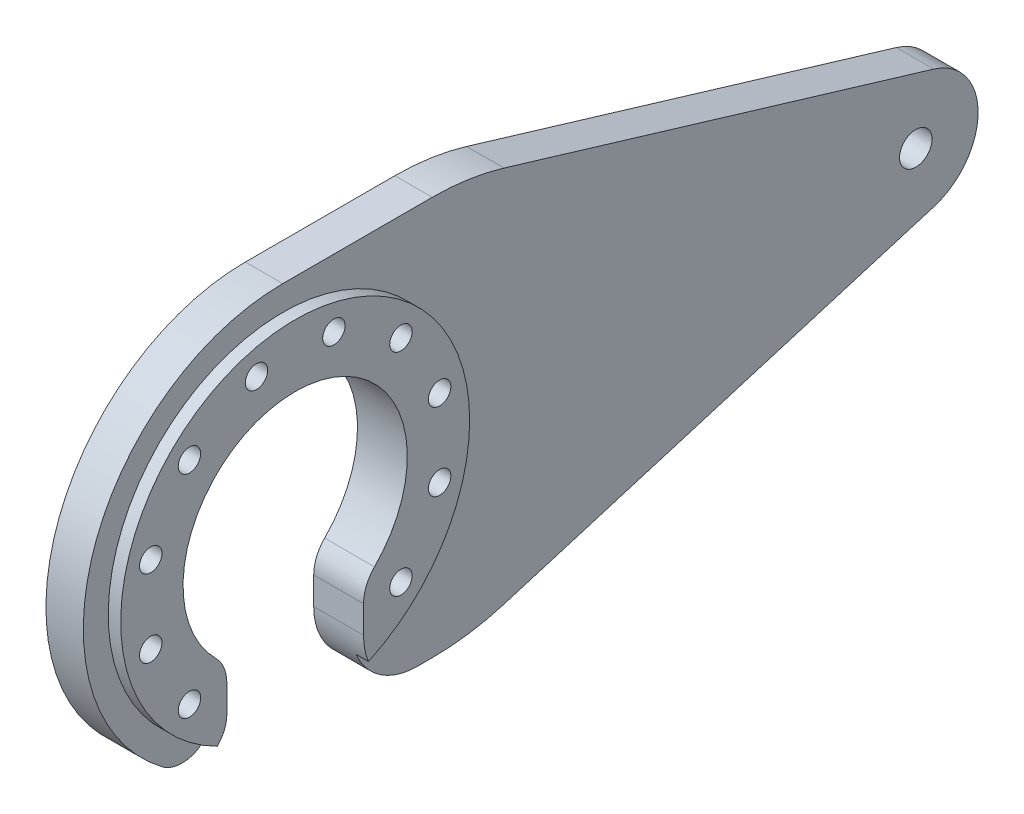
SolidWorks part; units mm, degrees
ref_plane "Front Plane" through (0, 0, 0) normal (0, 0, 1) x (1, 0, 0)
ref_plane "Top Plane" through (0, 0, 0) normal (0, 1, 0) x (1, 0, 0)
ref_plane "Right Plane" through (0, 0, 0) normal (1, 0, 0) x (0, 0, -1)
sketch "Sketch1" plane through (0, 0, 0) normal (-1, 0, 0) x (0, 0, 1)
  circle A0 centre (0, 0) radius 22.5
  circle A1 centre (0, 0) radius 35
  circle A2 centre (21.2132, -21.2132) radius 2.25 construction
  circle A3 centre (28.9778, -7.7646) radius 2.25 construction
  circle A4 centre (28.9778, 7.7646) radius 2.25 construction
  circle A5 centre (21.2132, 21.2132) radius 2.25 construction
  circle A6 centre (7.7646, 28.9778) radius 2.25 construction
  circle A7 centre (-7.7646, 28.9778) radius 2.25 construction
  circle A8 centre (-21.2132, 21.2132) radius 2.25 construction
  circle A9 centre (-28.9778, 7.7646) radius 2.25 construction
  circle A10 centre (-28.9778, -7.7646) radius 2.25 construction
  circle A11 centre (-21.2132, -21.2132) radius 2.25 construction
  circle A12 centre (-21.2132, -21.2132) radius 2.25
  circle A13 centre (-28.9778, -7.7646) radius 2.25
  circle A14 centre (-28.9778, 7.7646) radius 2.25
  circle A15 centre (-21.2132, 21.2132) radius 2.25
  circle A16 centre (-7.7646, 28.9778) radius 2.25
  circle A17 centre (7.7646, 28.9778) radius 2.25
  circle A18 centre (21.2132, 21.2132) radius 2.25
  circle A19 centre (28.9778, 7.7646) radius 2.25
  circle A20 centre (28.9778, -7.7646) radius 2.25
  circle A21 centre (21.2132, -21.2132) radius 2.25
  dimension "D1" = 45
  dimension "D2" = 70
extrude "Boss-Extrude1" add sketch "Sketch1" along normal blind 2.5
sketch "Sketch2" plane through (-2.5, 0, 0) normal (-1, 0, 0) x (0, 0, 1)
  line L0 (0, 40) -> (-30, 40)
  line L1 (-44.3935, 37.8835) -> (-130.5984, 11.9709)
  line L2 (-130.5984, -11.9709) -> (-44.3935, -37.8835)
  line L3 (-30, -40) -> (0, -40)
  arc A0 (-30, 40) -> (-44.3935, 37.8835) centre (-30, -10) ccw
  circle A1 centre (0, 0) radius 22.5
  circle A2 centre (0, 0) radius 22.5
  circle A3 centre (-21.2132, -21.2132) radius 2.25
  circle A4 centre (-21.2132, -21.2132) radius 2.25
  circle A5 centre (-28.9778, -7.7646) radius 2.25
  circle A6 centre (-28.9778, -7.7646) radius 2.25
  circle A7 centre (-28.9778, 7.7646) radius 2.25
  circle A8 centre (-28.9778, 7.7646) radius 2.25
  circle A9 centre (-21.2132, 21.2132) radius 2.25
  circle A10 centre (-21.2132, 21.2132) radius 2.25
  circle A11 centre (-7.7646, 28.9778) radius 2.25
  circle A12 centre (-7.7646, 28.9778) radius 2.25
  circle A13 centre (7.7646, 28.9778) radius 2.25
  circle A14 centre (7.7646, 28.9778) radius 2.25
  circle A15 centre (21.2132, 21.2132) radius 2.25
  circle A16 centre (21.2132, 21.2132) radius 2.25
  circle A17 centre (28.9778, 7.7646) radius 2.25
  circle A18 centre (28.9778, 7.7646) radius 2.25
  circle A19 centre (28.9778, -7.7646) radius 2.25
  circle A20 centre (28.9778, -7.7646) radius 2.25
  circle A21 centre (21.2132, -21.2132) radius 2.25
  circle A22 centre (21.2132, -21.2132) radius 2.25
  arc A23 (-130.5984, 11.9709) -> (-130.5984, -11.9709) centre (-127, 0) ccw
  arc A24 (-44.3935, -37.8835) -> (-30, -40) centre (-30, 10) ccw
  arc A25 (0, -40) -> (0, 40) centre (0, 0) ccw
  circle A26 centre (-127, 0) radius 3.2639
  dimension "D12" = 40
  dimension "D13" = 12.5
  dimension "D14" = 50
  dimension "D17" = 6.5278
  dimension "D15" = 30
  dimension "D16" = 127
  dimension "D1" = 0
  dimension "D2" = 0
  dimension "D3" = 0
  dimension "D4" = 0
  dimension "D5" = 0
  dimension "D6" = 0
  dimension "D7" = 0
  dimension "D8" = 0
  dimension "D9" = 0
  dimension "D10" = 0
  dimension "D11" = 0
extrude "Boss-Extrude2" add sketch "Sketch2" along normal offset from surface (7.5 mm away) 10 up to face at (0, 0, 35)
sketch "Sketch3" plane through (0, 0, 0) normal (1, 0, 0) x (0, 0, -1)
  line L0 (30, -40) -> (0, -40) construction
  line L1 (26.9985, -40) -> (0, -40)
  line L3 (13.7132, -21.2132) -> (13.7132, -26.7147)
  line L4 (-13.7132, -21.2132) -> (-13.7132, -26.7147)
  circle A0 centre (0, 0) radius 22.5 construction
  arc A1 (-15.9099, -15.9099) -> (15.9099, -15.9099) centre (0, 0) ccw
  arc A2 (-15.9099, -15.9099) -> (-13.7132, -21.2132) centre (-21.2132, -21.2132) cw
  arc A4 (13.7132, -21.2132) -> (15.9099, -15.9099) centre (21.2132, -21.2132) cw
  circle A5 centre (-21.2132, -21.2132) radius 2.25 construction
  arc A9 (13.7132, -26.7147) -> (26.9985, -40) centre (26.9985, -26.7147) ccw
  arc A10 (0, 40) -> (0, -40) centre (0, 0) ccw construction
  arc A11 (-24.1352, -31.8982) -> (0, -40) centre (0, 0) ccw
  arc A12 (-13.7132, -26.7147) -> (-24.1352, -31.8982) centre (-20.2132, -26.7147) cw
  point P15 (-23.6942, -32.2271)
  point P18 (0, 0)
  point P19 (13.7132, -26.868)
  dimension "D1" = 6.5
extrude "Cut-Extrude1" cut sketch "Sketch3" against normal through all
sketch "Sketch4" plane through (-10, 0, 0) normal (-1, 0, 0) x (0, 0, 1)
  circle A0 centre (-21.2132, -21.2132) radius 5
  circle A1 centre (-28.9778, -7.7646) radius 5
  circle A2 centre (-28.9778, 7.7646) radius 5
  circle A3 centre (-21.2132, 21.2132) radius 5
  circle A4 centre (-7.7646, 28.9778) radius 5
  circle A5 centre (7.7646, 28.9778) radius 5
  circle A6 centre (21.2132, 21.2132) radius 5
  circle A7 centre (28.9778, 7.7646) radius 5
  circle A8 centre (28.9778, -7.7646) radius 5
  circle A9 centre (21.2132, -21.2132) radius 5
  dimension "D1" = 10
extrude "Cut-Extrude2" cut sketch "Sketch4" against normal offset from surface (5 mm away) 5 up to face at (0, -10.7013, -0.0328)
